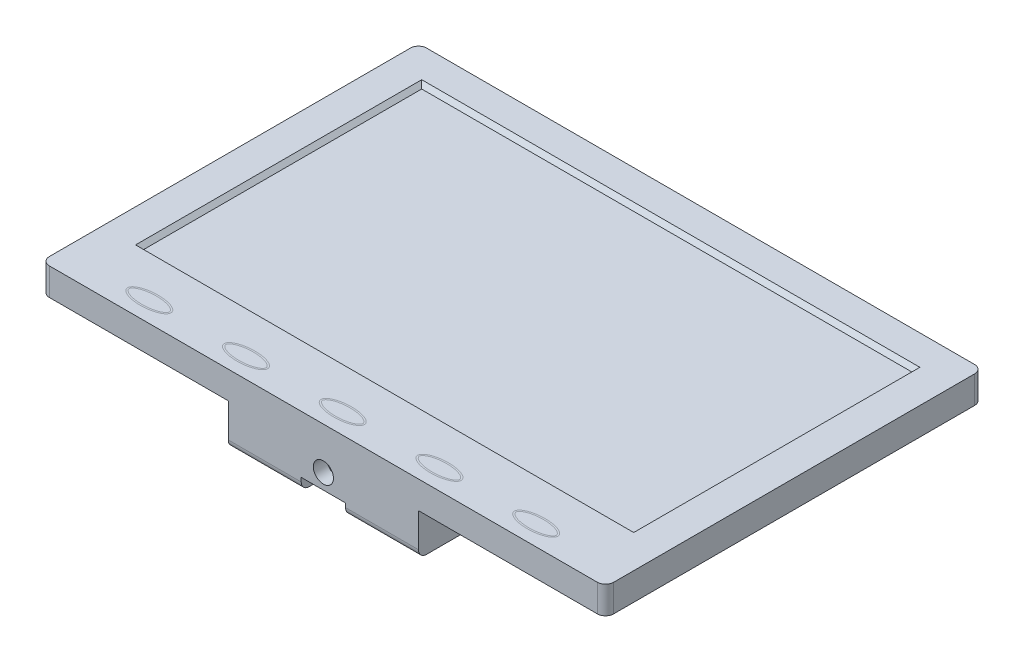
SolidWorks part; units mm, degrees
ref_plane "Front Plane" through (0, 0, 0) normal (0, 0, 1) x (1, 0, 0)
ref_plane "Top Plane" through (0, 0, 0) normal (0, 1, 0) x (1, 0, 0)
ref_plane "Right Plane" through (0, 0, 0) normal (1, 0, 0) x (0, 0, -1)
sketch "Sketch1" plane through (0, 0, 0) normal (0, 1, 0) x (1, 0, 0)
  line L1 (-88.9, 59.436) -> (88.9, 59.436)
  line L2 (-88.9, 59.436) -> (-88.9, -59.436)
  line L3 (-88.9, -59.436) -> (88.9, -59.436)
  line L4 (88.9, 59.436) -> (88.9, -59.436)
  line L5 (-88.9, 59.436) -> (88.9, -59.436) construction
  line L6 (-88.9, -59.436) -> (88.9, 59.436) construction
  point P0 (0, 0)
  dimension "D1" = 118.872
  dimension "D2" = 177.8
extrude "Boss-Extrude1" add sketch "Sketch1" along normal blind 8.636
sketch "Sketch2" plane through (0, 8.636, 0) normal (0, 1, 0) x (1, 0, 0)
  line L0 (-88.9, 59.436) -> (-88.9, -59.436) construction
  line L1 (-77.216, 48.768) -> (77.216, 48.768)
  line L2 (-77.216, 48.768) -> (-77.216, -38.862)
  line L3 (-77.216, -38.862) -> (77.216, -38.862)
  line L4 (77.216, 48.768) -> (77.216, -38.862)
  line L5 (88.9, -59.436) -> (88.9, 59.436) construction
  line L6 (-88.9, -59.436) -> (88.9, -59.436) construction
  line L7 (88.9, 59.436) -> (-88.9, 59.436) construction
  dimension "D1" = 11.684
  dimension "D2" = 11.684
  dimension "D3" = 20.574
  dimension "D4" = 10.668
extrude "Cut-Extrude1" cut sketch "Sketch2" against normal blind 1.27
chamfer "Chamfer1" distance 1.27 angle 45 4 edges at (77.216, 8.636, -4.953) (0, 8.636, 38.862) (-77.216, 8.636, -4.953) (0, 8.636, -48.768)
fillet "Fillet1" radius 2.54 4 edges at (88.9, 4.318, 59.436) (-88.9, 4.318, 59.436) (-88.9, 4.318, -59.436) (88.9, 4.318, -59.436)
sketch "Sketch3" plane through (0, 0, 0) normal (0, -1, 0) x (1, 0, 0)
  line L0 (-29.972, 59.436) -> (-29.972, 49.276)
  line L1 (-86.36, 59.436) -> (86.36, 59.436) construction
  line L2 (-29.972, 49.276) -> (-71.374, 49.276)
  line L3 (-71.374, 49.276) -> (-71.374, -48.26)
  line L4 (-71.374, -48.26) -> (71.374, -48.26)
  line L5 (71.374, -48.26) -> (71.374, 49.276)
  line L6 (71.374, 49.276) -> (29.972, 49.276)
  line L7 (29.972, 49.276) -> (29.972, 59.436)
  line L8 (-29.972, 59.436) -> (29.972, 59.436)
  line L10 (-88.9, -56.896) -> (-88.9, 56.896) construction
  dimension "D1" = 59.944
  dimension "D2" = 97.536
  dimension "D3" = 10.16
  dimension "D4" = 142.748
  dimension "D5" = 58.928
extrude "Boss-Extrude2" add sketch "Sketch3" along normal blind 13.208
sketch "Sketch4" plane through (0, 0, 59.436) normal (0, 0, 1) x (1, 0, 0)
  line L0 (-86.36, 8.636) -> (86.36, 8.636) construction
  line L3 (-29.972, -13.208) -> (-29.972, 0) construction
  circle A0 centre (0, -4.572) radius 3.175
  dimension "D2" = 6.35
  dimension "D1" = 13.208
  dimension "D3" = 29.972
extrude "Cut-Extrude2" cut sketch "Sketch4" against normal blind 4.2672
fillet "Fillet2" radius 2.54 1 edges at (0, -13.208, 59.436)
chamfer "Chamfer2" distance 13.208 angle 30 1 edges at (0, -13.208, -48.26) first distance on face at (0, -6.604, -48.26)
chamfer "Chamfer3" distance 13.208 angle 30 2 edges at (71.374, -13.208, 4.3208) (-71.374, -13.208, 4.3208) first distance on face at (71.374, -6.604, 2.4144) first distance on face at (-71.374, -6.604, 2.4144)
chamfer "Chamfer4" distance 13.208 angle 15 2 edges at (46.8602, -13.208, 49.276) (-46.8602, -13.208, 49.276) first distance on face at (48.7666, -6.604, 49.276) first distance on face at (-48.7666, -6.604, 49.276)
fillet "Fillet3" radius 2.54 9 edges at (67.5612, -6.604, 47.5065) (67.5612, -6.604, -44.4472) (-67.5612, -6.604, -44.4472) (63.7484, -13.208, 2.5513) (46.8602, -13.208, 45.7369) (0, -13.208, -40.6344) (-63.7484, -13.208, 2.5513) (-67.5612, -6.604, 47.5065) (-46.8602, -13.208, 45.7369)
sketch "Sketch5" plane through (0, -13.208, 0) normal (0, -1, 0) x (1, 0, 0)
  line L1 (63.5519, 34.4921) -> (88.9519, 34.4921)
  line L2 (63.5519, 34.4921) -> (63.5519, -27.4839)
  line L3 (63.5519, -27.4839) -> (88.9519, -27.4839)
  line L4 (88.9519, 34.4921) -> (88.9519, -27.4839)
  line L5 (-62.2819, -39.1679) -> (62.2819, -39.1679) construction
  line L7 (-63.5519, 34.4921) -> (-88.9519, 34.4921)
  line L8 (-63.5519, 34.4921) -> (-63.5519, -27.4839)
  line L9 (-63.5519, -27.4839) -> (-88.9519, -27.4839)
  line L10 (-88.9519, 34.4921) -> (-88.9519, -27.4839)
  line L11 (62.2819, -39.1679) -> (62.2819, 43.7879) construction
  line L12 (-62.2819, 43.7879) -> (-62.2819, -39.1679) construction
  dimension "D1" = 61.976
  dimension "D2" = 11.684
  dimension "D3" = 25.4
  dimension "D4" = 25.4
  dimension "D5" = 1.27
  dimension "D6" = 1.27
extrude "Cut-Extrude3" cut sketch "Sketch5" against normal up to surface (13.208 mm away) up to face at (0, 0, 11.066)
ref_plane "Plane1" through (0, -8.89, 0) normal (0, 1, 0) x (1, 0, 0)
sketch "Sketch14" plane through (0, -8.89, 0) normal (0, 1, 0) x (1, 0, 0)
  line L0 (-63.5519, 8.4339) -> (-49.5819, 8.4339)
  line L1 (-63.5519, 27.4839) -> (-63.5519, -34.4921) construction
  line L2 (-63.5519, 8.4339) -> (-63.5519, 14.7839)
  line L3 (-63.5519, 14.7839) -> (-49.5819, 14.7839)
  line L4 (-49.5819, 8.4339) -> (-43.2319, 8.4339)
  line L6 (-71.374, 27.4839) -> (-64.4816, 27.4839) construction
  arc A0 (-43.2319, 8.4339) -> (-49.5819, 14.7839) centre (-49.5819, 8.4339) ccw
  dimension "D2" = 13.97
  dimension "D3" = 19.05
  dimension "D1" = 6.35
revolve "Revolve4" add sketch "Sketch14" angle 360 about L0
sketch "Sketch15" plane through (63.5519, 0, 0) normal (1, 0, 0) x (0, 0, -1)
  line L2 (39.1679, -13.208) -> (-43.7879, -13.208) construction
  line L3 (-34.4921, 0) -> (27.4839, 0) construction
  line L4 (27.4839, 0) -> (27.4839, -12.8677) construction
  circle A0 centre (18.5939, -6.604) radius 3.175
  dimension "D1" = 6.35
  dimension "D2" = 6.604
  dimension "D3" = 6.604
  dimension "D4" = 8.89
extrude "Cut-Extrude4" cut sketch "Sketch15" against normal blind 8.89
sketch "Sketch16" plane through (54.6619, 0, 0) normal (1, 0, 0) x (0, 0, -1)
  circle A0 centre (18.5939, -6.604) radius 2.921
  circle A1 centre (18.5939, -6.604) radius 1.778
  dimension "D2" = 5.842
  dimension "D1" = 3.556
extrude "Boss-Extrude4" add sketch "Sketch16" along normal blind 8.89
fillet "Fillet4" radius 0.254 2 edges at (63.5519, -6.604, -21.5149) (63.5519, -6.604, -20.3719)
sketch "Sketch17" plane through (0, -13.208, 0) normal (0, -1, 0) x (-1, 0, 0)
  line L0 (41.5809, 17.5779) -> (41.5809, 32.8179) construction
  line L1 (41.1999, 17.5779) -> (41.1999, 32.8179)
  line L2 (41.9619, 17.5779) -> (41.9619, 32.8179)
  line L3 (62.2819, 39.1679) -> (-62.2819, 39.1679) construction
  line L4 (62.2819, 13.0898) -> (62.2819, 39.1679) construction
  arc A0 (41.1999, 17.5779) -> (41.9619, 17.5779) centre (41.5809, 17.5779) ccw
  arc A1 (41.9619, 32.8179) -> (41.1999, 32.8179) centre (41.5809, 32.8179) ccw
  point P2 (41.5809, 25.1979)
  dimension "D1" = 0.762
  dimension "D2" = 15.24
  dimension "D3" = 13.97
  dimension "D4" = 20.32
extrude "Cut-Extrude5" cut sketch "Sketch17" against normal blind 12.7
pattern_linear "LPattern1" count 30 spacing 3.175 along (1, 0, 0) of "Cut-Extrude5"
sketch "Sketch18" plane through (-63.5519, 0, 0) normal (-1, 0, 0) x (0, 0, 1)
  line L1 (-3.4841, -12.8677) -> (34.4921, -12.8677) construction
  line L2 (34.4921, 0) -> (34.4921, -12.8677) construction
  circle A0 centre (24.3321, -7.5337) radius 2.794
  dimension "D1" = 5.588
  dimension "D2" = 5.334
  dimension "D3" = 10.16
extrude "Cut-Extrude6" cut sketch "Sketch18" against normal blind 12.7
sketch "Sketch19" plane through (-50.8519, 0, 0) normal (-1, 0, 0) x (0, 0, 1)
  circle A0 centre (24.3321, -7.5337) radius 0.762
  dimension "D1" = 1.524
extrude "Boss-Extrude5" add sketch "Sketch19" along normal blind 8.89
fillet "Fillet5" radius 0.762 1 edges at (-59.7419, -7.5337, 25.0941)
sketch "Sketch20" plane through (-50.8519, 0, 0) normal (-1, 0, 0) x (0, 0, 1)
  circle A0 centre (24.3321, -7.5337) radius 1.016
  dimension "D1" = 2.032
extrude "Boss-Extrude6" add sketch "Sketch20" along normal blind 1.27
sketch "Sketch22" plane through (-63.5519, 0, 0) normal (-1, 0, 0) x (0, 0, 1)
  line L0 (-3.4841, -12.8677) -> (34.4921, -12.8677) construction
  line L1 (-1.0679, -4.9937) -> (11.6321, -4.9937)
  line L2 (-1.0679, -4.9937) -> (-1.0679, -10.0737)
  line L3 (-1.0679, -10.0737) -> (11.6321, -10.0737)
  line L4 (11.6321, -4.9937) -> (11.6321, -10.0737)
  line L5 (-1.0679, -4.9937) -> (11.6321, -10.0737) construction
  line L6 (-1.0679, -10.0737) -> (11.6321, -4.9937) construction
  circle A0 centre (24.3321, -7.5337) radius 2.794 construction
  point P0 (5.2821, -7.5337)
  dimension "D1" = 12.7
  dimension "D2" = 5.08
  dimension "D3" = 5.334
  dimension "D4" = 12.7
extrude "Cut-Extrude7" cut sketch "Sketch22" against normal blind 12.7
sketch "Sketch24" plane through (-50.8519, 0, 0) normal (-1, 0, 0) x (0, 0, 1)
  line L1 (-0.4329, -7.9147) -> (10.9971, -7.9147)
  line L2 (-0.4329, -7.9147) -> (-0.4329, -9.1847)
  line L3 (-0.4329, -9.1847) -> (10.9971, -9.1847)
  line L4 (10.9971, -7.9147) -> (10.9971, -9.1847)
  line L5 (-0.4329, -7.9147) -> (10.9971, -9.1847) construction
  line L6 (-0.4329, -9.1847) -> (10.9971, -7.9147) construction
  line L7 (-1.0679, -4.9937) -> (-1.0679, -10.0737) construction
  line L8 (-1.0679, -10.0737) -> (11.6321, -10.0737) construction
  point P0 (5.2821, -8.5497)
  dimension "D1" = 1.524
  dimension "D2" = 1.27
  dimension "D3" = 11.43
  dimension "D4" = 6.35
extrude "Boss-Extrude7" add sketch "Sketch24" along normal blind 11.43
chamfer "Chamfer5" distance 0.508 angle 30 4 edges at (-62.2819, -9.1847, 5.2821) (-62.2819, -8.5497, -0.4329) (-62.2819, -7.9147, 5.2821) (-62.2819, -8.5497, 10.9971) first distance on face at (-56.5669, -9.1847, 5.2821) first distance on face at (-56.5669, -8.5497, -0.4329) first distance on face at (-56.5669, -7.9147, 5.2821) first distance on face at (-56.5669, -8.5497, 10.9971)
sketch "Sketch25" plane through (63.5519, 0, 0) normal (1, 0, 0) x (0, 0, -1)
  line L0 (-7.4411, -9.8197) -> (7.7989, -9.8197)
  line L1 (7.7989, -9.8197) -> (7.7989, -6.0097)
  line L2 (7.7989, -6.0097) -> (4.7193, -4.2317)
  line L3 (4.7193, -4.2317) -> (-4.3615, -4.2317)
  line L4 (-4.3615, -4.2317) -> (-7.4411, -6.0097)
  line L5 (-7.4411, -6.0097) -> (-7.4411, -9.8197)
  line L6 (-34.4921, -12.8677) -> (27.4839, -12.8677) construction
  circle A0 centre (18.5939, -6.604) radius 3.175 construction
  point P10 (0.1789, -4.2317)
  point P11 (0.1789, -9.8197)
  dimension "D1" = 15.24
  dimension "D2" = 10.795
  dimension "D3" = 3.048
  dimension "D4" = 3.81
  dimension "D5" = 210
  dimension "D6" = 5.588
  dimension "D7" = 210
extrude "Cut-Extrude8" cut sketch "Sketch25" against normal blind 12.7
fillet "Fillet6" radius 0.508 2 edges at (57.2019, -9.8197, -7.7989) (57.2019, -9.8197, 7.4411)
sketch "Sketch26" plane through (63.5519, 0, 0) normal (1, 0, 0) x (0, 0, -1)
  line L0 (-21.6651, -7.0257) -> (-14.0451, -7.0257)
  line L1 (-14.0451, -7.0257) -> (-14.0451, -5.2477)
  line L2 (-14.0451, -5.2477) -> (-14.5531, -4.6689)
  line L3 (-14.5531, -4.6689) -> (-14.5531, -3.9777)
  line L4 (-14.5531, -3.9777) -> (-21.1571, -3.9777)
  line L5 (-21.1571, -3.9777) -> (-21.1571, -4.6689)
  line L6 (-21.1571, -4.6689) -> (-21.6651, -5.2477)
  line L7 (-21.6651, -5.2477) -> (-21.6651, -7.0257)
  line L8 (-34.4921, -12.8677) -> (27.4839, -12.8677) construction
  line L9 (-7.4411, -6.0097) -> (-7.4411, -9.3117) construction
  point P0 (-17.8551, -3.9777)
  point P11 (-17.8551, -7.0257)
  dimension "D1" = 7.62
  dimension "D2" = 5.842
  dimension "D3" = 3.048
  dimension "D4" = 1.778
  dimension "D5" = 6.604
  dimension "D6" = 6.604
extrude "Cut-Extrude9" cut sketch "Sketch26" against normal blind 6.35
fillet "Fillet7" radius 0.254 4 edges at (60.3769, -3.9777, 14.5531) (60.3769, -3.9777, 21.1571) (60.3769, -7.0257, 14.0451) (60.3769, -7.0257, 21.6651)
sketch "Sketch27" plane through (0, 8.636, 0) normal (0, 1, 0) x (1, 0, 0)
  line L0 (-86.36, -59.436) -> (86.36, -59.436) construction
  line L1 (-88.9, 56.896) -> (-88.9, -56.896) construction
  line L2 (-66.8111, -54.102) -> (-55.6169, -54.102) construction
  line L3 (-36.3311, -54.102) -> (-25.1369, -54.102) construction
  line L4 (-5.8511, -54.102) -> (5.3431, -54.102) construction
  line L5 (24.6289, -54.102) -> (35.8231, -54.102) construction
  line L6 (55.1089, -54.102) -> (66.3031, -54.102) construction
  ellipse E0 centre (-61.214, -53.086) end of major axis (-54.356, -53.086) minor radius 2.794
  ellipse E1 centre (-30.734, -53.086) end of major axis (-37.592, -53.086) minor radius 2.794
  ellipse E2 centre (-0.254, -53.086) end of major axis (6.604, -53.086) minor radius 2.794
  ellipse E3 centre (30.226, -53.086) end of major axis (37.084, -53.086) minor radius 2.794
  ellipse E4 centre (60.706, -53.086) end of major axis (67.564, -53.086) minor radius 2.794
  point P10 (-54.864, -53.086)
  point P20 (-24.3838, -53.0866)
  point P29 (6.096, -53.086)
  point P38 (36.576, -53.086)
  point P49 (67.056, -53.086)
  dimension "D1" = 5.588
  dimension "D2" = 13.716
  dimension "D3" = 3.556
  dimension "D4" = 20.828
  dimension "D6" = 1.778
  dimension "D7" = 5
  dimension "D8" = 1.778
  dimension "D10" = 1.778
  dimension "D5" = 0.508
wrap "Wrap3" sketch "Sketch27" wrap type scribe source sketch "Sketch27" face at (0, 8.636, -4.953)
sketch "Sketch28" plane through (0, -13.208, 0) normal (0, -1, 0) x (1, 0, 0)
  line L0 (-3.81, 16.764) -> (3.81, 16.764)
  line L1 (3.81, 16.764) -> (3.81, 48.768)
  line L2 (3.81, 48.768) -> (6.985, 51.816)
  line L3 (6.985, 51.816) -> (6.985, 59.436)
  line L4 (-29.972, 59.436) -> (29.972, 59.436) construction
  line L5 (6.985, 59.436) -> (-6.985, 59.436)
  line L6 (-6.985, 59.436) -> (-6.985, 51.816)
  line L7 (-3.81, 16.764) -> (-3.81, 48.768)
  line L8 (-3.81, 48.768) -> (-6.985, 51.816)
  point P7 (0, 16.764)
  point P11 (0, 59.436)
  point P13 (-3.81, 31.2223)
  dimension "D1" = 13.97
  dimension "D2" = 7.62
  dimension "D3" = 32.004
  dimension "D4" = 3.048
  dimension "D5" = 7.62
extrude "Cut-Extrude10" cut sketch "Sketch28" against normal blind 3.81
fillet "Fillet8" radius 1.016 6 edges at (-6.985, -11.303, 51.816) (-3.81, -11.303, 48.768) (-3.81, -11.303, 16.764) (3.81, -11.303, 16.764) (3.81, -11.303, 48.768) (6.985, -11.303, 51.816)
